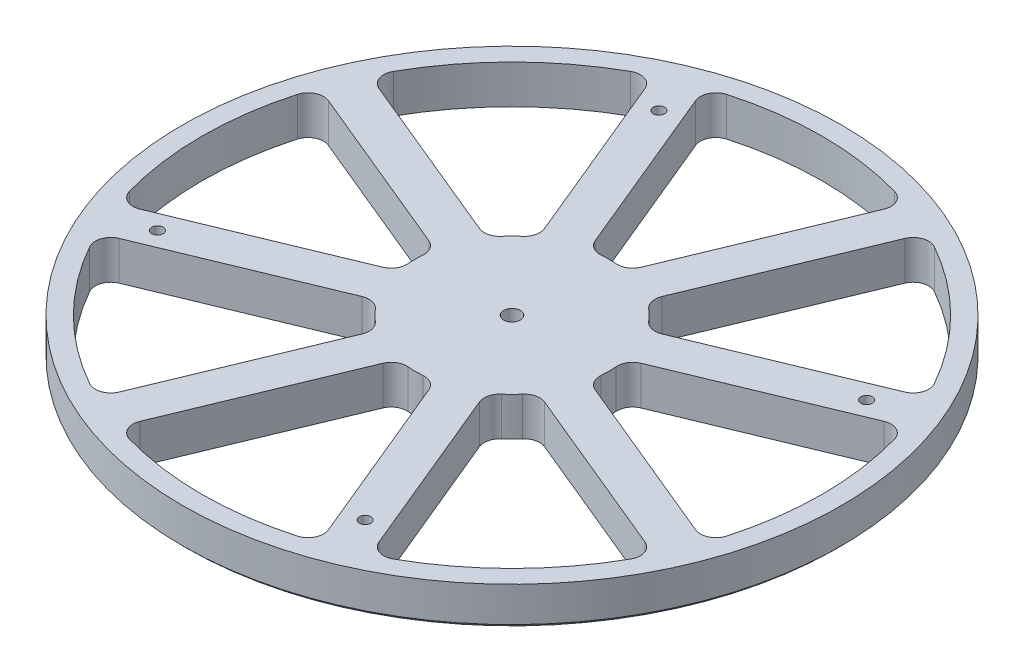
SolidWorks part; units mm, degrees
ref_plane "Front Plane" through (0, 0, 0) normal (0, 0, 1) x (1, 0, 0)
ref_plane "Top Plane" through (0, 0, 0) normal (0, 1, 0) x (1, 0, 0)
ref_plane "Right Plane" through (0, 0, 0) normal (1, 0, 0) x (0, 0, -1)
sketch "Sketch2" plane through (0, 0, 0) normal (1, 0, 0) x (0, 0, -1)
  line L0 (0, 0) -> (-84.9998, 0)
  line L1 (-84.9998, 0) -> (-84.9998, 10)
  line L2 (-84.9998, 10) -> (0, 10)
  line L5 (0, 10) -> (0, 0)
  dimension "D1" = 84.9998
  dimension "D2" = 10
ref_axis "Axis1" through (0, -0.75, 0) along (0, 1, 0)
revolve "Revolve1" add sketch "Sketch2" angle 360 about axis through (0, -0.75, 0) along (0, 1, 0)
hole_wizard "#32 (0.116) Diameter Hole1" positions "Sketch6" profile "Sketch7" hole size "#32" standard "ANSI Inch" end condition through all
sketch "Sketch6" plane through (0, 10, 0) normal (0, 1, 0) x (1, 0, 0)
  line L0 (0, 0) -> (-53.438, 129.0108) construction
  line L2 (0, 0) -> (0, 109.0908) construction
  point P0 (-26.7878, 64.6716)
  dimension "D1" = 22.5
  dimension "D2" = 70
sketch "Sketch7" plane through (-26.7878, 10, -64.6716) normal (1, 0, 0) x (0, 0, 1)
  line L0 (0, 0) -> (0, 10)
  line L1 (0, 10) -> (1.4732, 10)
  line L2 (1.4732, 10) -> (1.4732, 0)
  line L5 (1.4732, 0) -> (0, 0)
  line L11 (0, -6.35) -> (0, 107.95) construction
  dimension "Thru Hole Dia." = 2.9464
  dimension "Thru Hole Depth" = 10
pattern_circular "CirPattern3" count 4 over 360 about axis through (0, -0.75, 0) along (0, 1, 0) of "#32 (0.116) Diameter Hole1"
sketch "Sketch8" plane through (0, 10, 0) normal (0, 1, 0) x (1, 0, 0)
  line L4 (0, 0) -> (0, 93.9995) construction
  line L5 (0, 0) -> (113.8372, 0) construction
  line L6 (-4.7544, 24.5438) -> (-25.9354, 75.6791)
  line L7 (4.7544, 24.5438) -> (25.9354, 75.6791)
  line L8 (0, 0) -> (-26.7878, 64.6716) construction
  arc A0 (-4.7544, 24.5438) -> (4.7544, 24.5438) centre (0, 0) cw
  arc A1 (-25.9354, 75.6791) -> (25.9354, 75.6791) centre (0, 0) cw
  circle A2 centre (0, 0) radius 84.9998 construction
  dimension "D1" = 25
  dimension "D2" = 5
  dimension "D3" = 5
extrude "Cut-Extrude1" cut sketch "Sketch8" against normal through all
fillet "Fillet1" radius 4 4 edges at (4.7544, 5, -24.5438) (25.9354, 5, -75.6791) (-4.7544, 5, -24.5438) (-25.9354, 5, -75.6791)
pattern_circular "CirPattern4" count 8 over 360 about axis through (0, -0.75, 0) along (0, 1, 0) of "Cut-Extrude1", "Fillet1"
chamfer "Chamfer2" distance 1 angle 45 1 edges at (0, 0, -84.9998)
hole_wizard "#18 (0.1695) Diameter Hole1" positions "Sketch9" profile "Sketch11" hole size "#18" standard "ANSI Inch" end condition through all
sketch "Sketch9" plane through (0, 0, 0) normal (0, -1, 0) x (-1, 0, 0)
  point P0 (0, 0)
sketch "Sketch11" plane through (0, 0, 0) normal (1, 0, 0) x (0, 0, -1)
  line L0 (0, 0) -> (0, 10)
  line L1 (0, 10) -> (2.1526, 10)
  line L2 (2.1526, 10) -> (2.1526, 0)
  line L5 (2.1526, 0) -> (0, 0)
  line L11 (0, -6.35) -> (0, 107.95) construction
  dimension "Thru Hole Dia." = 4.3053
  dimension "Thru Hole Depth" = 10
